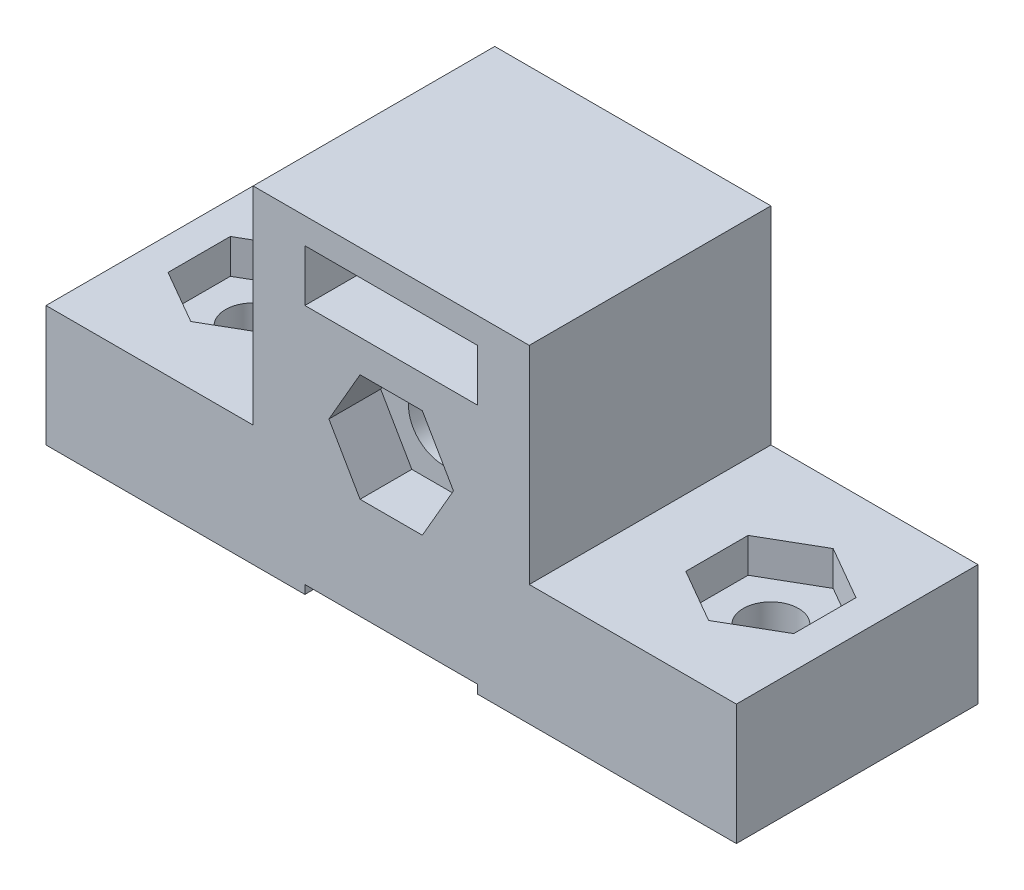
SolidWorks part; units mm, degrees
ref_plane "Front Plane" through (0, 0, 0) normal (0, 0, 1) x (1, 0, 0)
ref_plane "Top Plane" through (0, 0, 0) normal (0, 1, 0) x (1, 0, 0)
ref_plane "Right Plane" through (0, 0, 0) normal (1, 0, 0) x (0, 0, -1)
sketch "Sketch1" plane through (0, 0, 0) normal (0, 1, 0) x (1, 0, 0)
  line L1 (-20, 7) -> (20, 7)
  line L2 (-20, 7) -> (-20, -7)
  line L3 (-20, -7) -> (20, -7)
  line L4 (20, 7) -> (20, -7)
  line L5 (-20, 7) -> (20, -7) construction
  line L6 (-20, -7) -> (20, 7) construction
  point P0 (0, 0)
  dimension "D1" = 40
  dimension "D2" = 14
extrude "Boss-Extrude1" add sketch "Sketch1" along normal blind 19
sketch "Sketch2" plane through (0, 0, 7) normal (0, 0, 1) x (1, 0, 0)
  line L0 (0, 19) -> (0, 0) construction
  line L1 (-20, 19) -> (20, 19) construction
  line L3 (-5, 14.5) -> (5, 14.5)
  line L4 (-5, 14.5) -> (-5, 17.5)
  line L5 (-5, 17.5) -> (5, 17.5)
  line L6 (5, 14.5) -> (5, 17.5)
  line L7 (-5, 14.5) -> (5, 17.5) construction
  line L8 (-5, 17.5) -> (5, 14.5) construction
  line L9 (-5, -0.5) -> (5, -0.5)
  line L10 (-5, -0.5) -> (-5, 0.5)
  line L11 (-5, 0.5) -> (5, 0.5)
  line L12 (5, -0.5) -> (5, 0.5)
  line L13 (-5, -0.5) -> (5, 0.5) construction
  line L14 (-5, 0.5) -> (5, -0.5) construction
  point P5 (0, 16)
  dimension "D1" = 10
  dimension "D2" = 3
  dimension "D3" = 16
  dimension "D4" = 10
  dimension "D5" = 1
extrude "Cut-Extrude1" cut sketch "Sketch2" against normal blind 30
sketch "Sketch3" plane through (0, 0, 7) normal (0, 0, 1) x (1, 0, 0)
  line L0 (0, 19) -> (0, 0) construction
  line L1 (-20, 19) -> (20, 19) construction
  circle A0 centre (0, 9.5) radius 2
  dimension "D1" = 4
extrude "Cut-Extrude2" cut sketch "Sketch3" against normal through all
sketch "Sketch4" plane through (0, 19, 0) normal (0, 1, 0) x (1, 0, 0)
  line L0 (-20, 0) -> (20, 0) construction
  line L1 (-20, 7) -> (-20, -7) construction
  line L2 (20, -7) -> (20, 7) construction
  line L3 (0, 7) -> (0, -7) construction
  line L4 (20, 7) -> (-20, 7) construction
  line L5 (-20, -7) -> (20, -7) construction
  circle A0 centre (-15, 0) radius 1.6
  circle A1 centre (15, 0) radius 1.6
  dimension "D1" = 3.2
  dimension "D2" = 15
extrude "Cut-Extrude3" cut sketch "Sketch4" against normal through all
sketch "Sketch8" plane through (0, 0, 0) normal (0, -1, 0) x (-1, 0, 0)
  line L0 (-5, 7) -> (-5, -7) construction
  line L1 (5, -7) -> (-5, -7)
  line L2 (5, -7) -> (5, -6)
  line L3 (5, -6) -> (-5, -6)
  line L4 (-5, -7) -> (-5, -6)
  dimension "D1" = 1
extrude "Boss-Extrude2" [suppressed] add sketch "Sketch8" against normal up to next
sketch "Sketch9" plane through (0, 19, 0) normal (0, 1, 0) x (1, 0, 0)
  line L0 (0, 7) -> (0, -7) construction
  line L1 (-15, 3.6084) -> (-18.125, 1.8042)
  line L2 (-18.125, 1.8042) -> (-18.125, -1.8042)
  line L3 (-18.125, -1.8042) -> (-15, -3.6084)
  line L4 (-15, -3.6084) -> (-11.875, -1.8042)
  line L5 (-11.875, -1.8042) -> (-11.875, 1.8042)
  line L6 (-11.875, 1.8042) -> (-15, 3.6084)
  line L7 (20, 7) -> (-20, 7) construction
  line L8 (-20, -7) -> (20, -7) construction
  line L9 (11.875, 1.8042) -> (15, 3.6084)
  line L10 (11.875, -1.8042) -> (11.875, 1.8042)
  line L11 (15, -3.6084) -> (11.875, -1.8042)
  line L12 (18.125, -1.8042) -> (15, -3.6084)
  line L13 (18.125, 1.8042) -> (18.125, -1.8042)
  line L14 (15, 3.6084) -> (18.125, 1.8042)
  circle A0 centre (-15, 0) radius 3.125 construction
  circle A1 centre (15, 0) radius 3.125 construction
  dimension "D1" = 6.25
extrude "Cut-Extrude4" cut sketch "Sketch9" against normal offset from surface (14 mm away) 5 up to face at (15, 0, -1.6)
sketch "Sketch10" plane through (0, 0, 7) normal (0, 0, 1) x (1, 0, 0)
  line L1 (1.8042, 12.625) -> (-1.8042, 12.625)
  line L2 (-1.8042, 12.625) -> (-3.6084, 9.5)
  line L3 (-3.6084, 9.5) -> (-1.8042, 6.375)
  line L4 (-1.8042, 6.375) -> (1.8042, 6.375)
  line L5 (1.8042, 6.375) -> (3.6084, 9.5)
  line L6 (3.6084, 9.5) -> (1.8042, 12.625)
  circle A0 centre (0, 9.5) radius 3.125 construction
  dimension "D1" = 6.25
extrude "Cut-Extrude5" cut sketch "Sketch10" against normal blind 3
sketch "Sketch11" plane through (0, 0, 7) normal (0, 0, 1) x (1, 0, 0)
  line L0 (0, 19) -> (0, 0) construction
  line L1 (-20, 19) -> (-8, 19)
  line L2 (-20, 19) -> (-20, 7)
  line L3 (-20, 7) -> (-8, 7)
  line L4 (-8, 19) -> (-8, 7)
  line L5 (-20, 19) -> (20, 19) construction
  line L6 (-20, 0) -> (-5, 0) construction
  line L7 (8, 19) -> (8, 7)
  line L8 (20, 7) -> (8, 7)
  line L9 (20, 19) -> (20, 7)
  line L10 (20, 19) -> (8, 19)
  dimension "D1" = 8
  dimension "D2" = 7
extrude "Cut-Extrude6" cut sketch "Sketch11" against normal through all
equation "\"X-ROD-SPACING\"=45"
equation "\"Y-ROD-SPACING\"=75"
equation "\"Z-ROD-SPACING\"=17.5"
equation "\"Y-BED-OFFSET\"=2"
equation "\"Y-BED-ROD-INSET\"=3.5"
equation "\"Y-BED-SCREW-SPACING\"=209"
equation "\"Y-BED-SCREW-CUTOUT-SLOT-HEIGHT\"=2.5"
equation "\"T-SLOT-NUT-FILLET-RADIUS\"=0.5"
equation "\"T-SLOT-SCREW-SHAFT-RADIUS\"=1.55"
equation "\"T-SLOT-SCREW-SHAFT-CUTOUT-LENGTH\"=11"
equation "\"T-SLOT-NUT-DEPTH\"=3.5"
equation "\"T-SLOT-NUT-WIDTH\"=2.85"
equation "\"T-SLOT-NUT-END-DISTANCE\"=8"
equation "\"ACRYLIC-THICKNESS\"=10"
equation "\"ACRYLIC-THICKNESS2\"=4.5"
equation "\"ACRYLIC-TAB-CUTOUT-SIZE\"=\"ACRYLIC-THICKNESS\"+\"ACRYLIC-TAB-TOLERANCE\"*2"
equation "\"ACRYLIC-TAB-TOLERANCE\"=-.05"
equation "\"ACRYLIC-TAB-WIDTH\"=\"ACRYLIC-THICKNESS\""
equation "\"ACRYLIC-M3-HOLE\"=2.9"
equation "\"SMOOTHROD-CAP-SCREW-DISTANCE\"=20"
equation "\"FRAME-WIDTH-INNER\"=370"
equation "\"NEMA17-HOLE-SPACING\"=31"
equation "\"NEMA17-CENTRAL-CUTOUT\"=22.5"
equation "\"Z-BRACKET-REACH\"=57"
equation "\"Z-ROD-INSET\"=13.5"
equation "\"TOP-BRACKET-SPACING\"=40"
equation "\"SMOOTHROD-X-LENGTH\"=350"
equation "\"SMOOTHROD-Y-LENGTH\"=350"
equation "\"SMOOTHROD-Z-LENGTH\"=350"
equation "\"SMOOTHROD-TIGHTENING-HEADROOM\"=.25"
equation "\"LEADSCREW-Z-LENGTH\"=300"
equation "\"SCREW-LENGTH-FRAME\"=\"ACRYLIC-THICKNESS\" + 10"
equation "\"SCREW-LENGTH-MOTOR\"=\"ACRYLIC-THICKNESS\" + 5"
equation "\"SCREW-LENGTH-EXTRUDER\"=28"
equation "\"SCREW-HEAD-RADIUS\"=6"
equation "\"PRINTED-M3-HOLE\"=3.5"
equation "\"PRINTED-X-SMOOTHROD-DIAMETER\"=8.8"
equation "\"PRINTED-X-SMOOTHROD-CUTOUT\"=10"
equation "\"PRINTED-X-BASE-HEIGHT\"=10"
equation "\"PRINTED-LM8UU-CUTOUT-SIZE\"=15.5"
equation "\"PRINTED-LM8UU-CUTOUT-LENGTH\"=24.5"
equation "\"PRINTED-X-IDLER-HEIGHT\"=16"
equation "\"PSU-MOUNTING-WIDTH\"=95"
equation "\"PSU-MOUNTING-HEIGHT\"=177"
equation "\"Y-BELT-TO-ROD-DISTANCE\"=20"
equation "\"SPOOL-HOLDER-ROD-SPACING\"=150"
equation "\"ACRYLIC-X-CARRIAGE-WIDTH\"=55"
equation "\"ACRYLIC-X-CARRIAGE-HEIGHT\"=75"
equation "\"ACRYLIC-X-CARRIAGE-LM8UU-CUTOUT-WIDTH\"=24.25"
equation "\"ACRYLIC-X-CARRIAGE-LM8UU-CUTOUT-HEIGHT\"=11.0"
equation "\"ACRYLIC-X-CARRIAGE-SCREW-SPACING-X\"=15"
equation "\"ACRYLIC-X-CARRIAGE-SCREW-SPACING-Y\"=33"
equation "\"ACRYLIC-X-CARRIAGE-CENTER-TAB-SPACING\"=14"
equation "\"ACRYLIC-X-CARRIAGE-EXTRUDER-OFFSET\"=26"
equation "\"ACRYLIC-X-CARRIAGE-EXTRUDER-ANGLE\"=90"
equation "\"ACRYLIC-X-CARRIAGE-EXTRUDER-SHELF-DEPTH\"=\"ACRYLIC-X-CARRIAGE-EXTRUDER-OFFSET\" + 28"
equation "\"ACRYLIC-X-CARRIAGE-EXTRUDER-BRACE-SPACING\"=23"
equation "\"ACRYLIC-X-CARRIAGE-EXTRUDER-BRACE-TAB-OFFSET\"=20"
equation "\"ACRYLIC-X-CARRIAGE-EXTRUDER-BRACE-HEIGHT\"=35"
equation "\"ACRYLIC-X-CARRIAGE-EXTRUDER-BRACE-SCREW-SPACING\"=22"
equation "\"ACRYLIC-X-CARRIAGE-DUAL-WIDTH-MULTIPLIER\"=1.65"
equation "\"ACRYLIC-X-CARRIAGE-DUAL-HOTEND-SPACING\"=42"
equation "\"ACRYLIC-X-CARRIAGE-DUAL-WIDTH\"=75"
equation "\"ACRYLIC-X-CARRIAGE-DUAL-HOTEND-SEPARATION\"=36"
equation "\"ACRYLIC-X-CARRIAGE-DUAL-MOUNT-PLATE-DEPTH\"=75"
equation "\"ACRYLIC-X-CARRIAGE-DUAL-MOUNT-BRACE-WIDTH\"=33"
equation "\"ACRYLIC-X-CARRIAGE-DUAL-MOUNT-SCREW-WIDTH\"=40"
equation "\"BLOWER-FAN-WIDTH\"=15"
equation "\"PRINTED-M3-NUT-AF\"=6.25"
equation "\"D1@Sketch9\"=\"PRINTED-M3-NUT-AF\""
equation "\"D1@Sketch10\"=\"PRINTED-M3-NUT-AF\""
